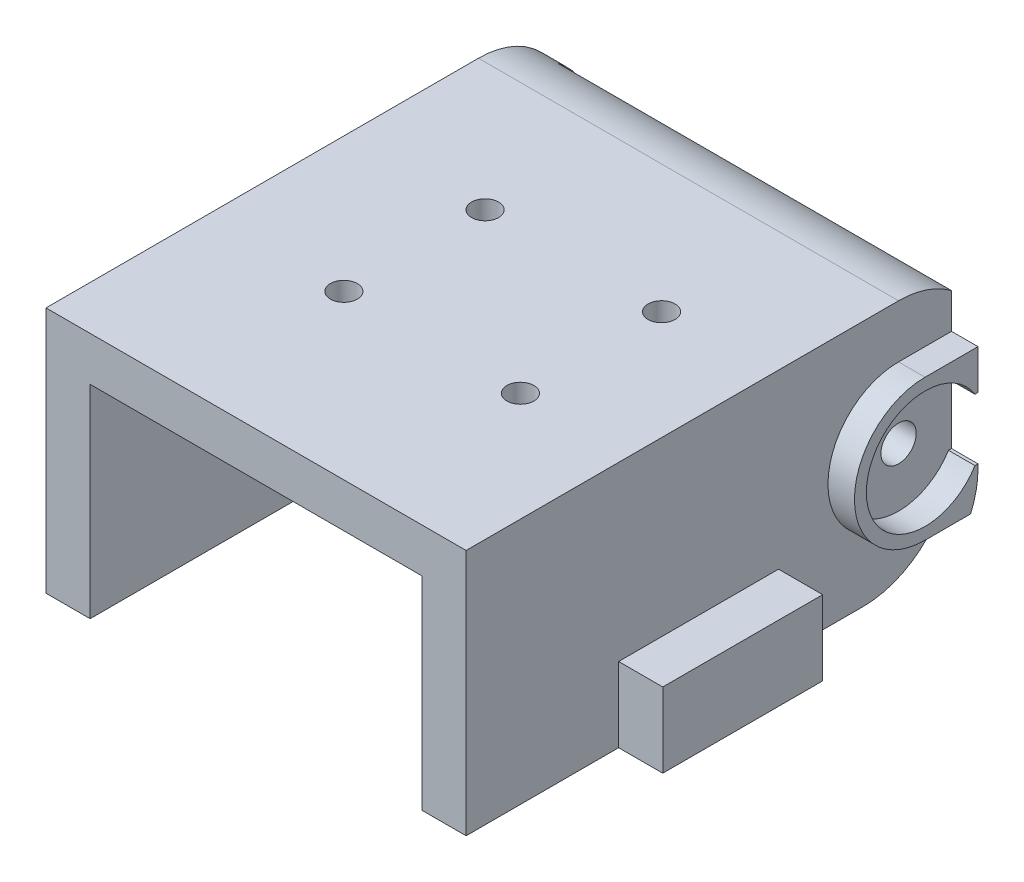
SolidWorks part; units mm, degrees
ref_plane "Front Plane" through (0, 0, 0) normal (0, 0, 1) x (1, 0, 0)
ref_plane "Top Plane" through (0, 0, 0) normal (0, 1, 0) x (1, 0, 0)
ref_plane "Right Plane" through (0, 0, 0) normal (1, 0, 0) x (0, 0, -1)
sketch "Sketch1" plane through (0, 0, 0) normal (0, 0, 1) x (1, 0, 0)
  line L1 (-23.8, 14) -> (23.8, 14)
  line L2 (-23.8, 14) -> (-23.8, -14)
  line L3 (-23.8, -14) -> (23.8, -14)
  line L4 (23.8, 14) -> (23.8, -14)
  line L5 (-23.8, 14) -> (23.8, -14) construction
  line L6 (-23.8, -14) -> (23.8, 14) construction
  point P0 (0, 0)
  dimension "D1" = 47.6
  dimension "D2" = 28
extrude "Boss-Extrude1" add sketch "Sketch1" along normal blind 55
sketch "Sketch3" plane through (23.8, 0, 0) normal (1, 0, 0) x (0, 0, -1)
  line L0 (0, -14) -> (0, 14) construction
  line L1 (-55, 14) -> (0, 14) construction
  circle A0 centre (-6, 0) radius 2
  dimension "D1" = 4
  dimension "D2" = 6
  dimension "D3" = 14
extrude "Cut-Extrude1" cut sketch "Sketch3" against normal blind 3
sketch "Sketch4" plane through (23.8, 0, 0) normal (1, 0, 0) x (0, 0, -1)
  line L0 (-55, -14) -> (0, -14) construction
  line L1 (-37.7174, -14) -> (-19.6014, -14)
  line L2 (-37.7174, -14) -> (-37.7174, -5.5367)
  line L3 (-37.7174, -5.5367) -> (-19.6014, -5.5367)
  line L4 (-19.6014, -14) -> (-19.6014, -5.5367)
extrude "Boss-Extrude2" add sketch "Sketch4" along normal blind 5
sketch "Sketch5" plane through (23.8, 0, 0) normal (1, 0, 0) x (0, 0, -1)
  line L1 (-6, 6.65) -> (2.4931, 6.65)
  line L2 (-6, 6.65) -> (-6, -6.5)
  line L3 (-6, -6.5) -> (2.4931, -6.5)
  line L4 (2.4931, 6.65) -> (2.4931, -6.5)
  line L5 (-6, 8) -> (2.4931, 8)
  line L6 (-6, 8) -> (-6, -8)
  line L7 (-6, -8) -> (2.4931, -8)
  line L8 (2.4931, 8) -> (2.4931, -8)
  line L9 (-6, 3.5) -> (2.4931, 3.5)
  line L10 (-6, 3.5) -> (-6, -3.5)
  line L11 (-6, -3.5) -> (2.4931, -3.5)
  line L12 (2.4931, 3.5) -> (2.4931, -3.5)
  circle A0 centre (-6, 0) radius 3.5
  circle A1 centre (-6, 0) radius 6.65
  circle A2 centre (-6, 0) radius 8
  line M6 (0, -14) -> (0, 14)
  dimension "D1" = 7
  dimension "D2" = 13.3
  dimension "D3" = 16
extrude "Boss-Extrude4" add sketch "Sketch5" along normal blind 3 contours L1 A2 L6 | A2 L1 L5 M6 | L6 A2 L3 | A2 L7 L3 M6 | A2 L1 M6 | A2 L3 M6 | A2 L1 A1 L9 M6 | L3 A2 L11 A1 M6 | L6 A2 A1 region at (23.8, 7.1941, 4.3118) region at (23.8, 0, 12.8289) region at (23.8, 5.54, 1.5903) region at (23.8, 7.4575, 1.6717) region at (23.8, 6.2169, 0.4946) region at (23.8, -7.1217, 4.189) region at (23.8, -7.4126, 1.6233) region at (23.8, -5.4229, 1.4013) region at (23.8, -6.1124, 0.4283)
sketch "Sketch6" plane through (-23.8, 0, 0) normal (-1, 0, 0) x (0, 0, 1)
  line L0 (0, 0) -> (6, 0) construction
  line L1 (0, 14) -> (0, -14) construction
  line L3 (6, 3.5) -> (-6.6051, 3.5)
  line L4 (6, 3.5) -> (6, -3.5)
  line L5 (6, -3.5) -> (-6.6051, -3.5)
  line L6 (-6.6051, 3.5) -> (-6.6051, -3.5)
  circle A0 centre (6, 0) radius 8
  circle A1 centre (6, 0) radius 10
  circle A2 centre (6, 0) radius 3.5
  line M2 (0, 14) -> (0, -14)
  dimension "D2" = 7
  dimension "D1" = 6
extrude "Boss-Extrude5" add sketch "Sketch6" along normal blind 3 contours A1 A0 M2 | L5 A1 A0 M2 | A1 L3 A0 M2 region at (-23.8, 5.2918, -1.3592) region at (-23.8, 6.6458, 0.2561) region at (-23.8, -5.2918, -1.3592)
sketch "Sketch8" plane through (0, 0, 0) normal (0, 0, -1) x (-1, 0, 0)
  line L0 (23.8, -14) -> (-23.8, -14) construction
  line L1 (23.8, 14) -> (20.8, 14)
  line L2 (23.8, 14) -> (23.8, -14)
  line L3 (23.8, -14) -> (20.8, -14)
  line L4 (20.8, 14) -> (20.8, -14)
  dimension "D1" = 3
extrude "Boss-Extrude7" add sketch "Sketch8" along normal blind 4
fillet "Fillet1" radius 10 2 edges at (-22.3, 14, -4) (1.5, -14, 0)
fillet "Fillet2" radius 10 1 edges at (-22.3, -14, -4)
ref_plane "Plane1" through (33.8, 0, 0) normal (1, 0, 0) x (0, 0, -1)
sketch "Sketch9" plane through (0, 14, 0) normal (0, 1, 0) x (1, 0, 0)
  line L1 (-23.8, -55) -> (-23.8, -6) construction
  line L2 (-20.8, 0) -> (23.8, 0) construction
  circle A0 centre (-8.55, -20.5) radius 1.5302
  circle A1 centre (11.45, -20.5) radius 1.5302
  circle A2 centre (11.45, -36.5) radius 1.5302
  circle A3 centre (-8.55, -36.5) radius 1.5302
  dimension "D1" = 20.5
  dimension "D2" = 15.25
  dimension "D5" = 20
  dimension "D6" = 16
  dimension "D7" = 20
  dimension "D3" = 2
  dimension "D4" = 2
extrude "Cut-Extrude2" cut sketch "Sketch9" against normal through all
sketch "Sketch10" plane through (0, 0, 55) normal (0, 0, 1) x (1, 0, 0)
  line L6 (-23.8, -14) -> (23.8, -14) construction
  line L7 (-18.8, -14) -> (18.8, -14)
  line L8 (-18.8, -14) -> (-18.8, 9)
  line L9 (-18.8, 9) -> (18.8, 9)
  line L10 (18.8, -14) -> (18.8, 9)
  line L11 (23.8, 14) -> (-23.8, 14) construction
  line L12 (-23.8, 14) -> (-23.8, -14) construction
  line L13 (23.8, -14) -> (23.8, 14) construction
  dimension "D1" = 5
  dimension "D2" = 5
  dimension "D3" = 5
extrude "Cut-Extrude4" cut sketch "Sketch10" against normal blind 40
